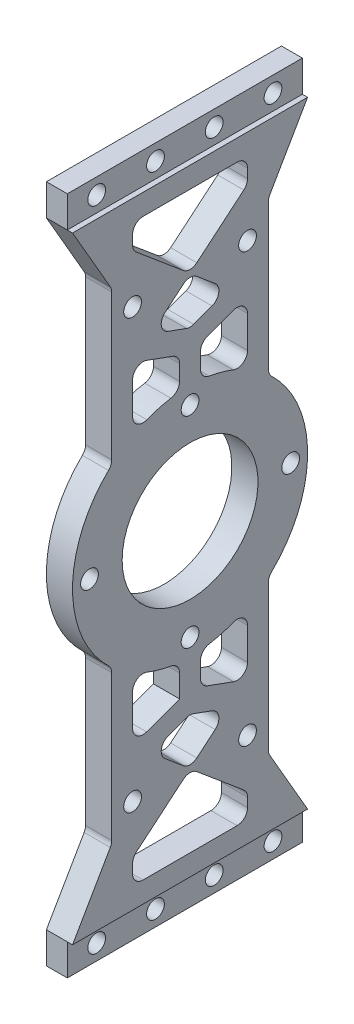
SolidWorks part; units mm, degrees
material "Сплав 2024"
ref_plane "Спереди" through (0, 0, 0) normal (0, 0, 1) x (1, 0, 0)
ref_plane "Сверху" through (0, 0, 0) normal (0, 1, 0) x (1, 0, 0)
ref_plane "Справа" through (0, 0, 0) normal (1, 0, 0) x (0, 0, -1)
sketch "Эскиз1" plane through (0, 0, 0) normal (0, 1, 0) x (1, 0, 0)
  line L1 (0, 0) -> (5, 0)
  line L2 (0, 0) -> (0, -30)
  line L3 (0, -30) -> (5, -30)
  line L4 (5, 0) -> (5, -30)
  dimension "D1" = 5
  dimension "D2" = 30
extrude "Бобышка-Вытянуть1" add sketch "Эскиз1" along normal blind 130
sketch "Эскиз2" plane through (0, 0, 0) normal (-1, 0, 0) x (0, 0, 1)
  line L0 (30, 65) -> (0, 65) construction
  line L1 (30, 130) -> (30, 0) construction
  line L2 (0, 130) -> (0, 0) construction
  line L3 (15, 130) -> (15, 0) construction
  line L4 (0, 130) -> (30, 130) construction
  line L5 (0, 0) -> (30, 0) construction
  circle A0 centre (15, 65) radius 22.5
  dimension "D1" = 45
extrude "Бобышка-Вытянуть2" add sketch "Эскиз2" against normal up to surface (5 mm away) up to face at (5, 65, 15)
sketch "Эскиз3" plane through (0, 0, 0) normal (-1, 0, 0) x (0, 0, 1)
  circle A0 centre (15, 65) radius 13
  dimension "D1" = 26
extrude "Вырез-Вытянуть1" cut sketch "Эскиз3" against normal through all
sketch "Эскиз4" plane through (5, 0, 0) normal (-1, 0, 0) x (0, 0, 1)
  line L0 (15, 87.5) -> (15, 42.5) construction
  line L1 (15, 130) -> (15, 0) construction
  line L2 (37.5, 65) -> (-7.5, 65) construction
  circle A0 centre (15, 65) radius 19.25 construction
  circle A1 centre (15, 65) radius 22.5 construction
  dimension "D1" = 38.5
hole_wizard "Отверстие с зазором M33" positions "Эскиз6" profile "Эскиз5" hole size "M3" standard "Ansi Metric" end condition through all
sketch "Эскиз6" plane through (5, -25.0247, 7.2629) normal (-1, 0, 0) x (0, 0, 1)
  line L0 (7.7371, 112.5247) -> (7.7371, 67.5247) construction
  line L1 (30.2371, 90.0247) -> (-14.7629, 90.0247) construction
  circle A0 centre (7.7371, 90.0247) radius 19.25 construction
  point P0 (7.7371, 109.2747)
  point P6 (-11.5129, 90.0247)
  point P10 (7.7371, 70.7747)
  point P12 (26.9871, 90.0247)
sketch "Эскиз5" plane through (5, 84.25, 15) normal (0, 1, 0) x (0, 0, -1)
  line L0 (0, 0) -> (0, 5)
  line L1 (0, 5) -> (1.7, 5)
  line L2 (1.7, 5) -> (1.7, 0)
  line L5 (1.7, 0) -> (0, 0)
  line L11 (0, -6.35) -> (0, 107.95) construction
  dimension "Диаметр сквозного отверстия" = 3.4
  dimension "Глубина сквозного отверстия" = 5
sketch "Эскиз8" plane through (5, 0, 0) normal (1, 0, 0) x (0, 0, -1)
  line L0 (-15, 130) -> (-15, 0) construction
  line L1 (-30, 130) -> (0, 130) construction
  line L2 (-30, 0) -> (0, 0) construction
  line L3 (19.447, 65) -> (-49.447, 65) construction
  line L4 (0, 130) -> (0, 81.7705) construction
  line L5 (-26, 106) -> (-4, 106) construction
  line L6 (-26, 106) -> (-26, 24) construction
  line L7 (-26, 24) -> (-4, 24) construction
  line L8 (-4, 106) -> (-4, 24) construction
  line L9 (-26, 106) -> (-4, 24) construction
  line L10 (-26, 24) -> (-4, 106) construction
  point P8 (-15, 65)
  point P9 (-15, 65)
  dimension "D1" = 4
  dimension "D2" = 82
hole_wizard "Отверстие с зазором M32" positions "Эскиз10" profile "Эскиз9" hole size "M3" standard "Ansi Metric" end condition through all
sketch "Эскиз10" plane through (5, 0, 0) normal (1, 0, 0) x (0, 0, -1)
  point P0 (-26, 106)
  point P3 (-4, 106)
  point P6 (-4, 24)
  point P9 (-26, 24)
sketch "Эскиз9" plane through (5, 106, 26) normal (0, 1, 0) x (0, 0, -1)
  line L0 (0, 0) -> (0, 5)
  line L1 (0, 5) -> (1.7, 5)
  line L2 (1.7, 5) -> (1.7, 0)
  line L5 (1.7, 0) -> (0, 0)
  line L11 (0, -6.35) -> (0, 107.95) construction
  dimension "Диаметр сквозного отверстия" = 3.4
  dimension "Глубина сквозного отверстия" = 5
sketch "Эскиз11" plane through (5, 0, 0) normal (1, 0, 0) x (0, 0, -1)
  line L0 (-15, 130) -> (-15, 0) construction
  line L1 (-30, 130) -> (0, 130) construction
  line L2 (-30, 0) -> (0, 0) construction
  line L3 (-37.5, 124) -> (-30, 111.0096)
  line L4 (-37.5, 124) -> (7.5, 124) construction
  line L5 (-37.5, 124) -> (-37.5, 130)
  line L6 (-37.5, 130) -> (7.5, 130)
  line L7 (7.5, 124) -> (7.5, 130)
  line L8 (-37.5, 124) -> (7.5, 130) construction
  line L9 (-37.5, 130) -> (7.5, 124) construction
  line L10 (-30, 130) -> (-30, 81.7705) construction
  line L11 (-30, 111.0096) -> (0, 111.0096)
  line L12 (0, 130) -> (0, 81.7705) construction
  line L13 (0, 111.0096) -> (7.5, 124)
  line L14 (-37.5, 127) -> (7.5, 127) construction
  line L15 (-31.875, 130) -> (-31.875, 124) construction
  line L16 (-26.25, 130) -> (-26.25, 124) construction
  line L17 (-20.625, 130) -> (-20.625, 124) construction
  line L18 (-15, 130) -> (-15, 124) construction
  line L19 (-15, 65) -> (-5.455, 65) construction
  line L20 (-15, 0) -> (-15, 6) construction
  line L21 (-20.625, 0) -> (-20.625, 6) construction
  line L22 (-26.25, 0) -> (-26.25, 6) construction
  line L23 (-31.875, 0) -> (-31.875, 6) construction
  line L24 (-37.5, 3) -> (7.5, 3) construction
  line L25 (-37.5, 0) -> (7.5, 6) construction
  line L26 (-37.5, 6) -> (7.5, 0) construction
  line L27 (-37.5, 6) -> (7.5, 6) construction
  line L28 (0, 18.9904) -> (7.5, 6)
  line L29 (-30, 18.9904) -> (0, 18.9904)
  line L30 (7.5, 6) -> (7.5, 0)
  line L31 (-37.5, 0) -> (7.5, 0)
  line L32 (-37.5, 6) -> (-37.5, 0)
  line L33 (-37.5, 6) -> (-30, 18.9904)
  line L34 (-9.375, 130) -> (-9.375, 124) construction
  line L35 (-3.75, 130) -> (-3.75, 124) construction
  line L36 (1.875, 130) -> (1.875, 124) construction
  line L37 (-9.375, 0) -> (-9.375, 6) construction
  line L38 (-3.75, 0) -> (-3.75, 6) construction
  line L39 (1.875, 0) -> (1.875, 6) construction
  point P6 (-15, 127)
  point P45 (-15, 3)
  dimension "D1" = 6
  dimension "D2" = 45
  dimension "D3" = 120
  dimension "D4" = 5.625
  dimension "D5" = 5.625
  dimension "D6" = 5.625
  dimension "D7" = 5.625
  dimension "D8" = 5.625
  dimension "D9" = 5.625
  dimension "D10" = 5.625
extrude "Бобышка-Вытянуть3" add sketch "Эскиз11" against normal up to surface (5 mm away) up to face at (0, 106, 24.3)
hole_wizard "Отверстие с зазором M31" positions "Эскиз13" profile "Эскиз12" hole size "M3" standard "Ansi Metric" end condition through all
sketch "Эскиз13" plane through (5, 0, 0) normal (1, 0, 0) x (0, 0, -1)
  line L0 (-31.875, 130) -> (-31.875, 124) construction
  line L4 (-31.875, 0) -> (-31.875, 6) construction
  line L8 (1.875, 130) -> (1.875, 124) construction
  line L9 (-9.375, 130) -> (-9.375, 124) construction
  line L10 (-20.625, 130) -> (-20.625, 124) construction
  line L11 (1.875, 0) -> (1.875, 6) construction
  line L12 (-9.375, 0) -> (-9.375, 6) construction
  line L13 (-20.625, 0) -> (-20.625, 6) construction
  point P0 (-31.875, 127)
  point P4 (-20.625, 127)
  point P8 (-9.375, 127)
  point P12 (1.875, 127)
  point P16 (-31.875, 3)
  point P20 (-20.625, 3)
  point P24 (-9.375, 3)
  point P28 (1.875, 3)
sketch "Эскиз12" plane through (5, 127, 31.875) normal (0, 1, 0) x (0, 0, -1)
  line L0 (0, 0) -> (0, 5)
  line L1 (0, 5) -> (1.7, 5)
  line L2 (1.7, 5) -> (1.7, 0)
  line L5 (1.7, 0) -> (0, 0)
  line L11 (0, -6.35) -> (0, 107.95) construction
  dimension "Диаметр сквозного отверстия" = 3.4
  dimension "Глубина сквозного отверстия" = 5
sketch "Эскиз14" plane through (5, 0, 0) normal (1, 0, 0) x (0, 0, -1)
  line L1 (-37.5, 130) -> (7.5, 130)
  line L2 (-37.5, 130) -> (-37.5, 124)
  line L3 (-37.5, 124) -> (7.5, 124)
  line L4 (7.5, 130) -> (7.5, 124)
  line L5 (-37.5, 0) -> (7.5, 0)
  line L6 (-37.5, 0) -> (-37.5, 6)
  line L7 (-37.5, 6) -> (7.5, 6)
  line L8 (7.5, 0) -> (7.5, 6)
extrude "Вырез-Вытянуть2" cut sketch "Эскиз14" against normal blind 1
sketch "Эскиз15" plane through (5, 0, 0) normal (1, 0, 0) x (0, 0, -1)
  line L0 (-26, 0) -> (-26, 130) construction
  line L1 (-37.5, 0) -> (7.5, 0) construction
  line L2 (7.5, 130) -> (-37.5, 130) construction
  line L3 (-4, 130) -> (-4, 0) construction
  line L4 (-30, 48.2295) -> (-30, 18.9904) construction
  line L5 (0, 48.2295) -> (0, 18.9904) construction
  line L6 (-15, 65) -> (0, 65) construction
  line L7 (-17, 42.5891) -> (-17, 36.5058)
  line L8 (-13, 42.5891) -> (-13, 36.5058)
  line L9 (-15, 130) -> (-15, 0) construction
  line L10 (-26, 24) -> (-4, 24) construction
  line L11 (-17, 36.5058) -> (-26, 33.2301)
  line L12 (-26, 33.2301) -> (-26, 45.3722)
  line L13 (-13, 36.5058) -> (-4, 33.2301)
  line L14 (-4, 33.2301) -> (-4, 45.3722)
  line L15 (-15, 32.9771) -> (-22.4618, 30.2612)
  line L16 (-22.4618, 30.2612) -> (-15, 24)
  line L17 (-15, 24) -> (-7.5382, 30.2612)
  line L18 (-7.5382, 30.2612) -> (-15, 32.9771)
  line L19 (-26, 33.2301) -> (-15, 24) construction
  line L20 (-4, 33.2301) -> (-15, 24) construction
  line L21 (-30, 23.9) -> (0, 23.9) construction
  line L22 (-15, 23.9) -> (-26, 14.6699) construction
  line L23 (-15, 23.9) -> (-4, 14.6699) construction
  line L24 (-4, 14.6699) -> (-26, 14.6699) construction
  line L25 (-15, 23.9) -> (-26, 14.6699)
  line L26 (-35.1906, 10) -> (5.1906, 10) construction
  line L27 (-30, 18.9904) -> (-37.5, 6) construction
  line L28 (7.5, 6) -> (0, 18.9904) construction
  line L29 (7.5, 6) -> (-37.5, 6) construction
  line L30 (-26, 14.6699) -> (-26, 10)
  line L31 (-26, 10) -> (-4, 10)
  line L32 (-4, 10) -> (-4, 14.6699)
  line L33 (-4, 14.6699) -> (-15, 23.9)
  line L34 (-13, 87.4109) -> (-13, 93.4942)
  line L35 (-13, 93.4942) -> (-4, 96.7699)
  line L36 (-4, 96.7699) -> (-4, 84.6278)
  line L37 (-26, 96.7699) -> (-26, 84.6278)
  line L38 (-17, 93.4942) -> (-26, 96.7699)
  line L39 (-17, 87.4109) -> (-17, 93.4942)
  line L40 (-7.5382, 99.7388) -> (-15, 97.0229)
  line L41 (-15, 97.0229) -> (-22.4618, 99.7388)
  line L42 (-22.4618, 99.7388) -> (-15, 106)
  line L43 (-15, 106) -> (-7.5382, 99.7388)
  line L44 (-4, 120) -> (-4, 115.3301)
  line L45 (-4, 115.3301) -> (-15, 106.1)
  line L46 (-15, 106.1) -> (-26, 115.3301)
  line L47 (-26, 115.3301) -> (-26, 120)
  line L48 (-26, 120) -> (-4, 120)
  circle A0 centre (-15, 65) radius 22.5 construction
  arc A1 (-26, 45.3722) -> (-17, 42.5891) centre (-15, 65) ccw
  arc A2 (-13, 42.5891) -> (-4, 45.3722) centre (-15, 65) ccw
  arc A3 (-13, 87.4109) -> (-4, 84.6278) centre (-15, 65) cw
  arc A4 (-26, 84.6278) -> (-17, 87.4109) centre (-15, 65) cw
  point P22 (-26, 45.3722)
  point P23 (-4, 45.3722)
  point P40 (-15, 23.9)
  dimension "D5" = 110
  dimension "D1" = 4
  dimension "D2" = 4
  dimension "D3" = 4
  dimension "D4" = 2
  dimension "D6" = 100
  dimension "D7" = 4
  dimension "D8" = 0.1
  dimension "D9" = 4
  dimension "D10" = 100
extrude "Вырез-Вытянуть3" cut sketch "Эскиз15" against normal up to next
fillet "Скругление1" radius 2 8 edges at (2.5, 111.0096, 0) (2.5, 81.7705, 0) (2.5, 48.2295, 0) (2.5, 18.9904, 0) (2.5, 18.9904, 30) (2.5, 48.2295, 30) (2.5, 81.7705, 30) (2.5, 111.0096, 30)
fillet "Скругление2" radius 2 33 edges at (2.5, 14.6699, 4) (2.5, 10, 4) (2.5, 14.6699, 26) (2.5, 10, 26) (2.5, 24, 15) (2.5, 33.2301, 4) (2.5, 30.2612, 7.5382) (2.5, 30.2612, 22.4618) (2.5, 36.5058, 13) (2.5, 33.2301, 26) (2.5, 45.3722, 4) (2.5, 42.5891, 17) (2.5, 23.9, 15) (2.5, 32.9771, 15) (2.5, 45.3722, 26) (2.5, 42.5891, 13) (2.5, 84.6278, 26) (2.5, 96.7699, 26) (2.5, 87.4109, 13) (2.5, 93.4942, 13) (2.5, 84.6278, 4) (2.5, 96.7699, 4) (2.5, 93.4942, 17) (2.5, 87.4109, 17) (2.5, 99.7388, 7.5382) (2.5, 97.0229, 15) (2.5, 99.7388, 22.4618) (2.5, 106, 15) (2.5, 120, 4) (2.5, 115.3301, 4) (2.5, 106.1, 15) (2.5, 115.3301, 26) (2.5, 120, 26)
equation "\"D4@Эскиз11\"=\"D2@Эскиз11\"/8"
equation "\"D5@Эскиз11\"=\"D4@Эскиз11\""
equation "\"D6@Эскиз11\"=\"D4@Эскиз11\""
equation "\"D7@Эскиз11\"=\"D4@Эскиз11\""
equation "\"D8@Эскиз11\"=\"D4@Эскиз11\""
equation "\"D9@Эскиз11\"=\"D4@Эскиз11\""
equation "\"D10@Эскиз11\"=\"D4@Эскиз11\""
